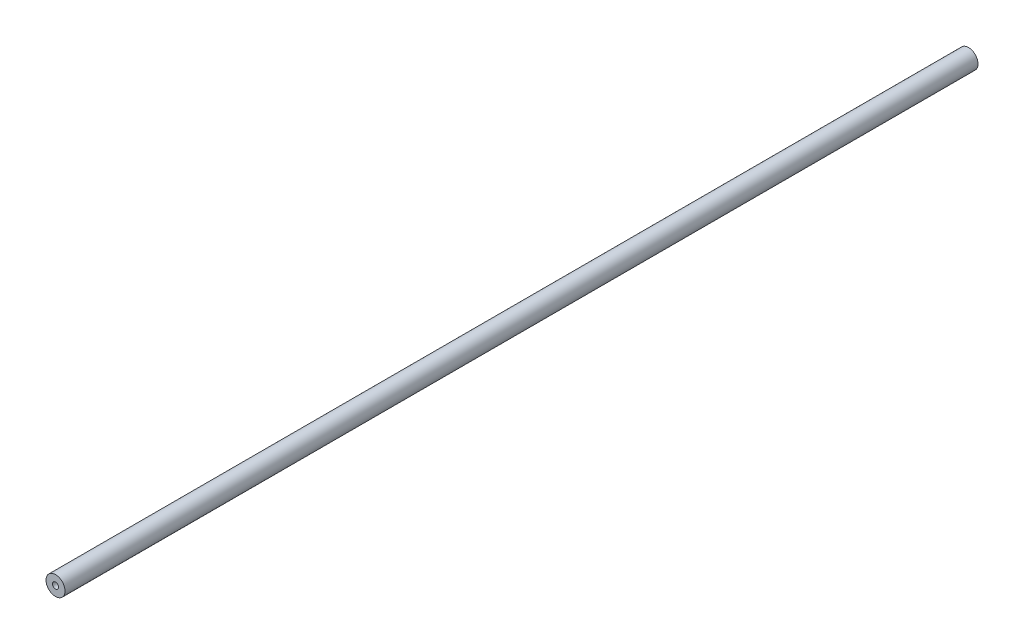
SolidWorks part; units mm, degrees
material "6061-T6 (SS)"
ref_plane "Front Plane" through (0, 0, 0) normal (0, 0, 1) x (1, 0, 0)
ref_plane "Top Plane" through (0, 0, 0) normal (0, 1, 0) x (1, 0, 0)
ref_plane "Right Plane" through (0, 0, 0) normal (1, 0, 0) x (0, 0, -1)
sketch "Sketch1" plane through (0, 0, 0) normal (0, 0, 1) x (1, 0, 0)
  circle A0 centre (0, 0) radius 6.35
  dimension "D1" = 12.7
extrude "Boss-Extrude1" add sketch "Sketch1" along normal blind 609.6
hole_wizard "#10-32 Tapped Hole1" positions "Sketch3" profile "Sketch2" tap size "#10-32" standard "ANSI Inch"
sketch "Sketch3" plane through (0, 0, 609.6) normal (0, 0, 1) x (1, 0, 0)
  point P0 (0, 0)
  point P1 (0, 0)
sketch "Sketch2" plane through (0, 0, 609.6) normal (1, 0, 0) x (0, -1, 0)
  line L0 (0, 0) -> (0, 14.9293)
  line L1 (0, 14.9293) -> (2.0193, 13.716)
  line L2 (2.0193, 13.716) -> (2.0193, 0)
  line L5 (2.0193, 0) -> (0, 0)
  line L10 (0, 14.9293) -> (-2.0193, 13.716) construction
  line L11 (0, -6.35) -> (0, 107.95) construction
  dimension "Tap Drill Dia." = 4.0386
  dimension "Tap Drill Depth" = 13.716
  dimension "Drill Angle" = 118
cosmetic thread "Hole Thread1"
hole_wizard "#10-32 Tapped Hole2" positions "Sketch5" profile "Sketch4" tap size "#10-32" standard "ANSI Inch"
sketch "Sketch5" plane through (0, 0, 0) normal (0, 0, -1) x (-1, 0, 0)
  point P0 (0, 0)
  point P1 (0, 0)
sketch "Sketch4" plane through (0, 0, 0) normal (1, 0, 0) x (0, 1, 0)
  line L0 (0, 0) -> (0, 14.9293)
  line L1 (0, 14.9293) -> (2.0193, 13.716)
  line L2 (2.0193, 13.716) -> (2.0193, 0)
  line L5 (2.0193, 0) -> (0, 0)
  line L10 (0, 14.9293) -> (-2.0193, 13.716) construction
  line L11 (0, -6.35) -> (0, 107.95) construction
  dimension "Tap Drill Dia." = 4.0386
  dimension "Tap Drill Depth" = 13.716
  dimension "Drill Angle" = 118
cosmetic thread "Hole Thread2" parameters "D1"=9.652, "D2"=4.826
